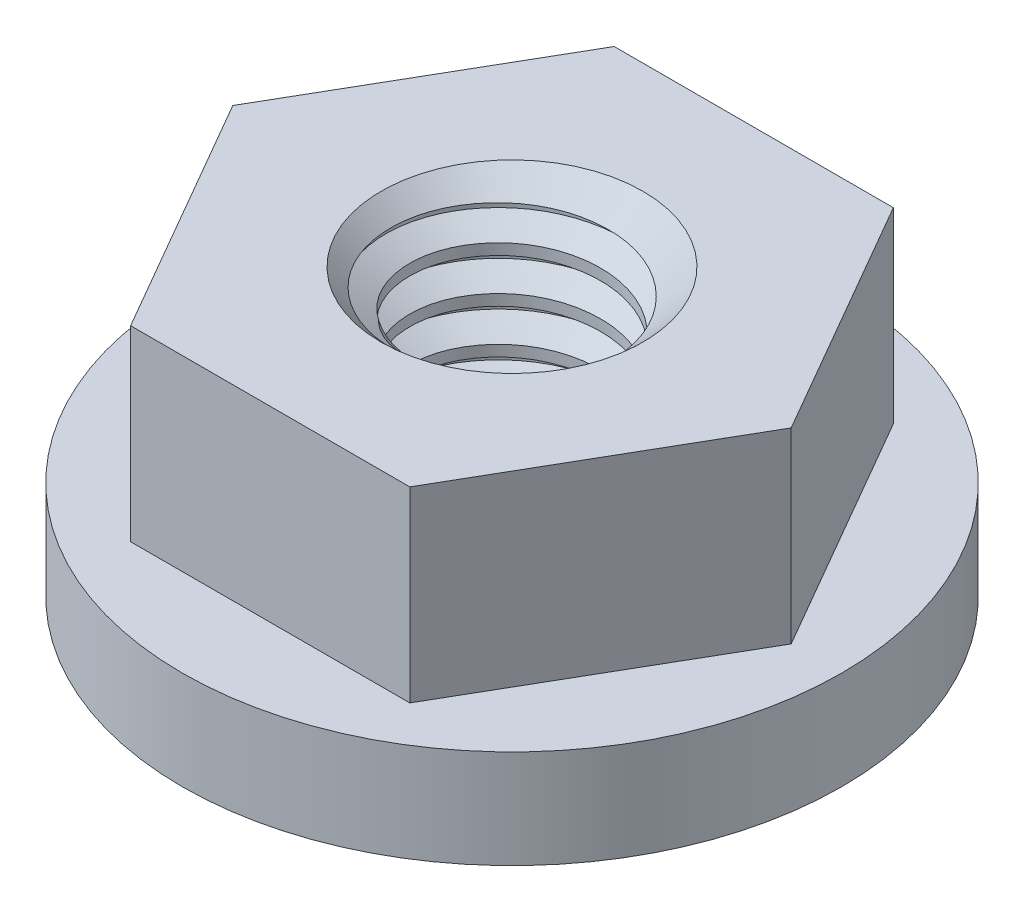
SolidWorks part; units mm, degrees
ref_plane "Front Plane" through (0, 0, 0) normal (0, 0, 1) x (1, 0, 0)
ref_plane "Top Plane" through (0, 0, 0) normal (0, 1, 0) x (1, 0, 0)
ref_plane "Right Plane" through (0, 0, 0) normal (1, 0, 0) x (0, 0, -1)
sketch "Sketch1" plane through (0, 0, 0) normal (0, 1, 0) x (1, 0, 0)
  circle A0 centre (0, 0) radius 5.9531
  dimension "D1" = 11.9062
extrude "Boss-Extrude1" add sketch "Sketch1" along normal blind 1.778
sketch "Sketch2" plane through (0, 1.778, 0) normal (0, 1, 0) x (1, 0, 0)
  line L1 (5.041, 0) -> (2.5205, 4.3656)
  line L2 (2.5205, 4.3656) -> (-2.5205, 4.3656)
  line L3 (-2.5205, 4.3656) -> (-5.041, 0)
  line L4 (-5.041, 0) -> (-2.5205, -4.3656)
  line L5 (-2.5205, -4.3656) -> (2.5205, -4.3656)
  line L6 (2.5205, -4.3656) -> (5.041, 0)
  circle A0 centre (0, 0) radius 4.3656 construction
  dimension "D1" = 8.7312
extrude "Boss-Extrude2" add sketch "Sketch2" along normal blind 3.3782
hole_wizard "Tap Drill for #8-32 Tap1" positions "Sketch3" profile "Sketch5" hole size "#8-32" standard "ANSI Inch" end condition through all
sketch "Sketch3" plane through (0, 5.1562, 0) normal (0, 1, 0) x (1, 0, 0)
  point P0 (0, 0)
sketch "Sketch5" plane through (0, 5.1562, 0) normal (1, 0, 0) x (0, 0, 1)
  line L0 (0, 0) -> (0, 5.1562)
  line L1 (0, 5.1562) -> (2.3622, 5.1562)
  line L2 (1.7272, 4.5212) -> (1.7272, 0.635)
  line L3 (1.7272, 0.635) -> (2.3622, 0)
  line L5 (2.3622, 0) -> (0, 0)
  line L6 (-1.7272, 0.635) -> (-2.3622, 0) construction
  line L7 (2.3622, 5.1562) -> (1.7272, 4.5212)
  line L8 (-2.3622, 5.1562) -> (-1.7272, 4.5212) construction
  line L11 (0, -6.35) -> (0, 107.95) construction
  dimension "Thru Hole Dia." = 3.4544
  dimension "Thru Hole Depth" = 5.1562
  dimension "Near C'Sink Dia." = 4.7244
  dimension "Near C'Sink Angle" = 90
  dimension "Far C'Sink Dia." = 4.7244
  dimension "Far C'Sink Angle" = 90
thread "Thread1" pitch 0.7937 method cut profile "Thread Profile1" start angle 0, offset 1.27, length 0, pitch 0.7937, diameter 3.4544
ref_plane "Plane1" through (-1.7272, 5.7912, 0) normal (0, 0, 1) x (-1, 0, 0)
sketch "Thread Profile1" plane through (-1.7272, 5.7912, 0) normal (0, 0, 1) x (-1, 0, 0)
  line L0 (0, 0) -> (0, 0.7937) construction
  line L1 (0, 0) -> (0.4296, 0.248)
  line L2 (0.4296, 0.248) -> (0.4296, 0.3473)
  line L3 (0.4296, 0.3473) -> (0, 0.5953)
  line L4 (0.4296, 0.2977) -> (0, 0.2977) construction
  line L11 (0, 0) -> (0, 0.5953)
  point P2 (0, 0)
  dimension "Pitch" = 0.7937
  dimension "Profile_Angle" = 60
  dimension "Profile_Land" = 0.0992
  dimension "Profile_Height" = 0.4296
